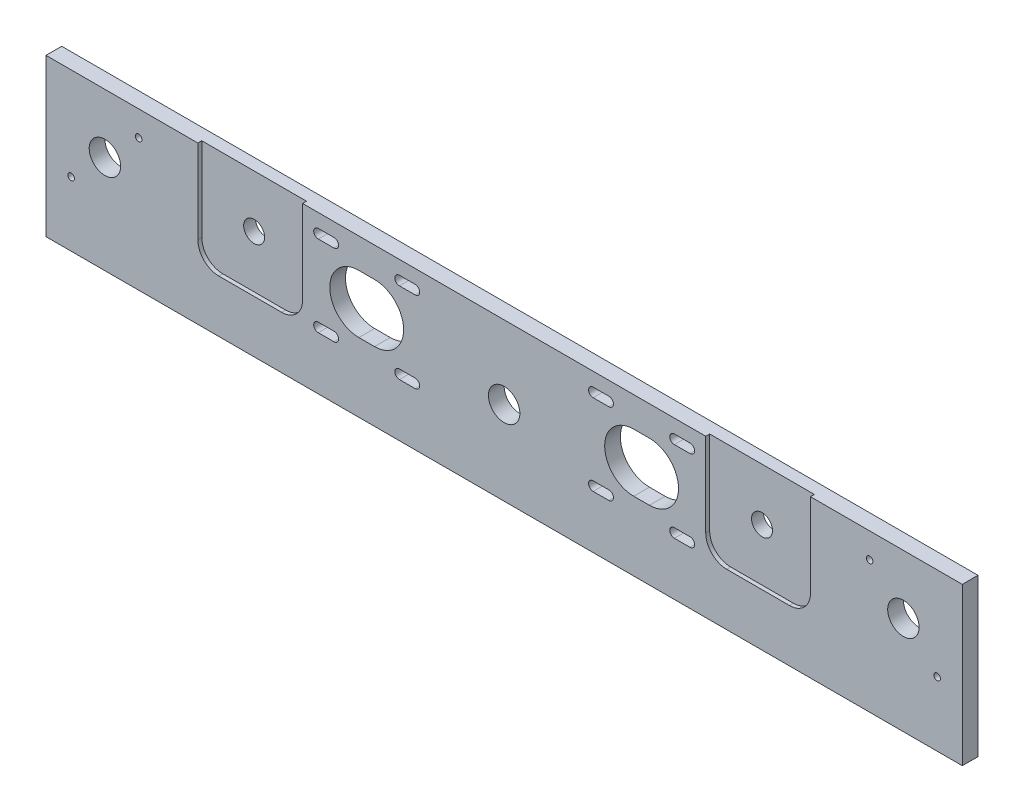
SolidWorks part; units mm, degrees
ref_plane "Alzado" through (0, 0, 0) normal (0, 0, 1) x (1, 0, 0)
ref_plane "Planta" through (0, 0, 0) normal (0, 1, 0) x (1, 0, 0)
ref_plane "Vista lateral" through (0, 0, 0) normal (1, 0, 0) x (0, 0, -1)
sketch "Croquis1" plane through (0, 0, 0) normal (0, 0, 1) x (1, 0, 0)
  line L1 (-350, -60) -> (0, -60)
  line L2 (-350, -60) -> (-350, 0)
  line L3 (-350, 0) -> (0, 0)
  line L4 (0, -60) -> (0, 0)
  dimension "D1" = 350
  dimension "D2" = 60
extrude "Saliente-Extruir1" add sketch "Croquis1" along normal blind 6 contours L3 L4 L1 L2
sketch "Croquis2" plane through (0, 0, 6) normal (0, 0, 1) x (1, 0, 0)
  line L0 (-350, -60) -> (-350, 0) construction
  line L1 (0, -60) -> (0, 0) construction
  line L2 (-350, -60) -> (0, -60) construction
  line L3 (-340.4047, -35.4047) -> (-314.5953, -9.5953) construction
  line L4 (-35.4047, -9.5953) -> (-9.5953, -35.4047) construction
  line L5 (-350, 0) -> (0, 0) construction
  circle A0 centre (-327.5, -22.5) radius 6
  circle A1 centre (-22.5, -22.5) radius 6
  circle A2 centre (-327.5, -22.5) radius 18.25 construction
  circle A4 centre (-314.5953, -9.5953) radius 1.25
  circle A5 centre (-340.4047, -35.4047) radius 1.25
  circle A6 centre (-22.5, -22.5) radius 18.25 construction
  circle A7 centre (-35.4047, -9.5953) radius 1.25
  circle A8 centre (-9.5953, -35.4047) radius 1.25
  circle A9 centre (-22.5, -22.5) radius 21 construction
  circle A10 centre (-327.5, -22.5) radius 21 construction
  dimension "D1" = 12
  dimension "D2" = 12
  dimension "D7" = 36.5
  dimension "D9" = 2.5
  dimension "D10" = 2.5
  dimension "D11" = 36.5
  dimension "D13" = 2.5
  dimension "D14" = 2.5
  dimension "D15" = 42
  dimension "D16" = 42
  dimension "D3" = 22.5
  dimension "D4" = 22.5
  dimension "D5" = 22.5
  dimension "D6" = 22.5
  dimension "D8" = 45
  dimension "D12" = 45
extrude "Cortar-Extruir1" cut sketch "Croquis2" against normal through all
sketch "Croquis3" plane through (0, 0, 6) normal (0, 0, 1) x (1, 0, 0)
  line L2 (-246, -7) -> (-240, -7) construction
  line L3 (-141, -7) -> (-135, -7) construction
  line L4 (-141, -5.25) -> (-135, -5.25)
  line L5 (-141, -8.75) -> (-135, -8.75)
  line L6 (-125.5, -22.5) -> (-119.5, -22.5) construction
  line L7 (-125.5, -11.4) -> (-119.5, -11.4)
  line L8 (-125.5, -33.6) -> (-119.5, -33.6)
  line L9 (-350, 0) -> (0, 0) construction
  line L10 (-141, -38) -> (-135, -38) construction
  line L11 (-141, -36.25) -> (-135, -36.25)
  line L12 (-141, -39.75) -> (-135, -39.75)
  line L13 (-110, -7) -> (-104, -7) construction
  line L14 (-110, -5.25) -> (-104, -5.25)
  line L15 (-110, -8.75) -> (-104, -8.75)
  line L16 (-110, -38) -> (-104, -38) construction
  line L17 (-110, -36.25) -> (-104, -36.25)
  line L18 (-110, -39.75) -> (-104, -39.75)
  line L19 (-246, -5.25) -> (-240, -5.25)
  line L20 (-246, -8.75) -> (-240, -8.75)
  line L21 (-230.5, -22.5) -> (-224.5, -22.5) construction
  line L22 (-230.5, -11.4) -> (-224.5, -11.4)
  line L23 (-230.5, -33.6) -> (-224.5, -33.6)
  line L24 (-246, -38) -> (-240, -38) construction
  line L25 (-246, -36.25) -> (-240, -36.25)
  line L26 (-246, -39.75) -> (-240, -39.75)
  line L27 (-215, -7) -> (-209, -7) construction
  line L28 (-215, -5.25) -> (-209, -5.25)
  line L29 (-215, -8.75) -> (-209, -8.75)
  line L30 (-215, -38) -> (-209, -38) construction
  line L31 (-215, -36.25) -> (-209, -36.25)
  line L32 (-215, -39.75) -> (-209, -39.75)
  line L33 (-350, 0) -> (0, 0) construction
  line L34 (0, -60) -> (0, 0) construction
  arc A2 (-246, -5.25) -> (-246, -8.75) centre (-246, -7) ccw
  arc A5 (-141, -5.25) -> (-141, -8.75) centre (-141, -7) ccw
  arc A6 (-135, -8.75) -> (-135, -5.25) centre (-135, -7) ccw
  arc A7 (-125.5, -11.4) -> (-125.5, -33.6) centre (-125.5, -22.5) ccw
  arc A8 (-119.5, -33.6) -> (-119.5, -11.4) centre (-119.5, -22.5) ccw
  circle A9 centre (-22.5, -22.5) radius 6 construction
  arc A11 (-141, -36.25) -> (-141, -39.75) centre (-141, -38) ccw
  arc A12 (-135, -39.75) -> (-135, -36.25) centre (-135, -38) ccw
  arc A13 (-110, -5.25) -> (-110, -8.75) centre (-110, -7) ccw
  arc A14 (-104, -8.75) -> (-104, -5.25) centre (-104, -7) ccw
  arc A15 (-110, -36.25) -> (-110, -39.75) centre (-110, -38) ccw
  arc A16 (-104, -39.75) -> (-104, -36.25) centre (-104, -38) ccw
  arc A17 (-240, -8.75) -> (-240, -5.25) centre (-240, -7) ccw
  arc A18 (-230.5, -11.4) -> (-230.5, -33.6) centre (-230.5, -22.5) ccw
  arc A19 (-224.5, -33.6) -> (-224.5, -11.4) centre (-224.5, -22.5) ccw
  arc A20 (-246, -36.25) -> (-246, -39.75) centre (-246, -38) ccw
  arc A21 (-240, -39.75) -> (-240, -36.25) centre (-240, -38) ccw
  arc A22 (-215, -5.25) -> (-215, -8.75) centre (-215, -7) ccw
  arc A23 (-209, -8.75) -> (-209, -5.25) centre (-209, -7) ccw
  arc A24 (-215, -36.25) -> (-215, -39.75) centre (-215, -38) ccw
  arc A25 (-209, -39.75) -> (-209, -36.25) centre (-209, -38) ccw
  circle A26 centre (-327.5, -22.5) radius 6 construction
  circle A27 centre (-175, -28) radius 6
  point P2 (-122.5, -22.5)
  point P12 (-138, -7)
  point P20 (-227.5, -22.5)
  point P23 (-138, -38)
  point P30 (-107, -7)
  point P37 (-107, -38)
  point P48 (-243, -7)
  point P55 (-243, -38)
  point P62 (-212, -7)
  point P69 (-212, -38)
  point P82 (0, 0)
  dimension "D5" = 1.75
  dimension "D4" = 22.2
  dimension "D9" = 15.5
  dimension "D18" = 1.75
  dimension "D19" = 1.75
  dimension "D20" = 1.75
  dimension "D21" = 1.75
  dimension "D36" = 1.75
  dimension "D37" = 1.75
  dimension "D38" = 1.75
  dimension "D41" = 12
  dimension "D1" = 100
  dimension "D2" = 22.5
  dimension "D3" = 6
  dimension "D6" = 15.5
  dimension "D7" = 6
  dimension "D8" = 15.5
  dimension "D10" = 15.5
  dimension "D11" = 15.5
  dimension "D12" = 15.5
  dimension "D13" = 6
  dimension "D14" = 6
  dimension "D15" = 6
  dimension "D16" = 15.5
  dimension "D17" = 15.5
  dimension "D22" = 6
  dimension "D23" = 6
  dimension "D24" = 22.2
  dimension "D25" = 15.5
  dimension "D26" = 15.5
  dimension "D27" = 15.5
  dimension "D28" = 15.5
  dimension "D29" = 15.5
  dimension "D30" = 15.5
  dimension "D31" = 6
  dimension "D32" = 6
  dimension "D33" = 6
  dimension "D34" = 15.5
  dimension "D35" = 15.5
  dimension "D39" = 100
  dimension "D40" = 22.5
  dimension "D42" = 175
  dimension "D43" = 28
extrude "Cortar-Extruir2" cut sketch "Croquis3" against normal through all
sketch "Croquis5" plane through (0, 0, 6) normal (0, 0, 1) x (1, 0, 0)
  line L0 (-350, 0) -> (0, 0) construction
  line L1 (-292, 0) -> (-252, 0)
  line L2 (-292, 0) -> (-292, -32)
  line L3 (-284, -40) -> (-260, -40)
  line L4 (-252, 0) -> (-252, -32)
  line L5 (-350, -60) -> (-350, 0) construction
  line L6 (-98, 0) -> (-58, 0)
  line L7 (-98, 0) -> (-98, -32)
  line L8 (-90, -40) -> (-66, -40)
  line L9 (-58, 0) -> (-58, -32)
  line L10 (0, -60) -> (0, 0) construction
  arc A0 (-260, -40) -> (-252, -32) centre (-260, -32) ccw
  arc A1 (-284, -40) -> (-292, -32) centre (-284, -32) cw
  arc A2 (-66, -40) -> (-58, -32) centre (-66, -32) ccw
  arc A3 (-90, -40) -> (-98, -32) centre (-90, -32) cw
  point P11 (-252, -40)
  dimension "D4" = 8
  dimension "D6" = 8
  dimension "D1" = 40
  dimension "D2" = 58
  dimension "D3" = 40
  dimension "D5" = 40
  dimension "D7" = 58
  dimension "D8" = 40
extrude "Cortar-Extruir4" cut sketch "Croquis5" against normal blind 1.5
sketch "Croquis7" plane through (0, 0, 4.5) normal (0, 0, 1) x (1, 0, 0)
  line L0 (-252, -32) -> (-252, 0) construction
  line L1 (-252, 0) -> (-292, 0) construction
  line L3 (-58, -32) -> (-58, 0) construction
  line L4 (-58, 0) -> (-98, 0) construction
  circle A0 centre (-272, -20) radius 4
  circle A1 centre (-78, -20) radius 4
  dimension "D1" = 8
  dimension "D4" = 8
  dimension "D5" = 20
  dimension "D2" = 20
  dimension "D3" = 20
  dimension "D6" = 20
extrude "Cortar-Extruir5" cut sketch "Croquis7" against normal through all
